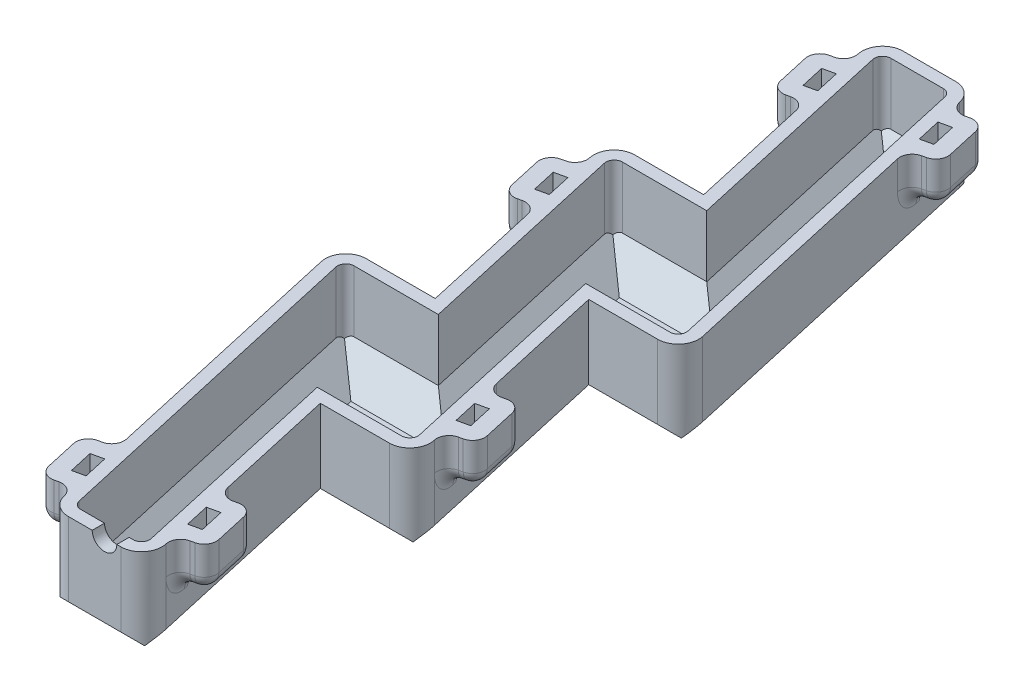
SolidWorks part; units mm, degrees
ref_plane "Front Plane" through (0, 0, 0) normal (0, 0, 1) x (1, 0, 0)
ref_plane "Top Plane" through (0, 0, 0) normal (0, 1, 0) x (1, 0, 0)
ref_plane "Right Plane" through (0, 0, 0) normal (1, 0, 0) x (0, 0, -1)
sketch "Sketch1" plane through (0, 0, 0) normal (0, 1, 0) x (1, 0, 0)
  line L12 (-21.7087, 45.3722) -> (1.3505, 45.3722)
  line L17 (-21.7087, 45.3722) -> (-1.3505, -45.3722)
  line L18 (1.3505, 45.3722) -> (21.7087, -45.3722)
  line L19 (-1.3505, -45.3722) -> (21.7087, -45.3722)
  line L20 (-10.1791, 45.3722) -> (10.1791, -45.3722) construction
  line L21 (32.5125, 9.2556) -> (9.4532, 9.2556)
  line L22 (32.5125, 9.2556) -> (12.1543, 100)
  line L23 (9.4532, 9.2556) -> (-10.905, 100)
  line L24 (12.1543, 100) -> (-10.905, 100)
  line L25 (20.9828, 9.2556) -> (0.6246, 100) construction
  line L26 (-32.5125, -9.2556) -> (-9.4532, -9.2556)
  line L27 (-32.5125, -9.2556) -> (-12.1543, -100)
  line L28 (-9.4532, -9.2556) -> (10.905, -100)
  line L29 (-12.1543, -100) -> (10.905, -100)
  line L30 (-20.9828, -9.2556) -> (-0.6246, -100) construction
  line L31 (1.051, -42.3722) -> (17.9611, -42.3722) construction
  line L32 (1.051, -42.3722) -> (-17.9611, 42.3722) construction
  line L33 (17.9611, -42.3722) -> (-1.051, 42.3722) construction
  line L34 (-17.9611, 42.3722) -> (-1.051, 42.3722) construction
  line L35 (-9.4532, -9.2556) -> (9.4532, 9.2556) construction
  line L36 (9.5061, -42.3722) -> (17.556, -40.5662) construction
  point P7 (0, 0)
  point P20 (-9.5061, 42.3722)
  point P21 (9.5061, -42.3722)
  point P26 (8.4551, 0)
  point P27 (0, 0)
  dimension "D1" = 93
  dimension "D3" = 200
  dimension "D4" = 3
  dimension "D5" = 3
  dimension "D6" = 85
  dimension "14.5" = 16.5
extrude "Boss-Extrude1" add sketch "Sketch1" along normal blind 25 contours L18 | L17 L18 | L17 | L27 region at (0, 0, 0) region at (10.8037, 0, -54.6278) region at (-10.8037, 0, 54.6278)
sketch "Sketch4" plane through (0, 25, 0) normal (0, 1, 0) x (1, 0, 0)
  line L0 (1.051, -42.3722) -> (17.9611, -42.3722)
  line L1 (1.051, -42.3722) -> (-17.9611, 42.3722)
  line L2 (17.9611, -42.3722) -> (-1.051, 42.3722)
  line L3 (-17.9611, 42.3722) -> (-1.051, 42.3722)
  line L4 (11.8547, 12.2556) -> (28.7648, 12.2556)
  line L5 (11.8547, 12.2556) -> (-7.1574, 97)
  line L6 (28.7648, 12.2556) -> (9.7527, 97)
  line L7 (-7.1574, 97) -> (9.7527, 97)
  line L8 (1.2977, 97) -> (20.3098, 12.2556) construction
  line L9 (-28.7648, -12.2556) -> (-11.8547, -12.2556)
  line L10 (-28.7648, -12.2556) -> (-9.7527, -97)
  line L11 (-11.8547, -12.2556) -> (7.1574, -97)
  line L12 (-9.7527, -97) -> (7.1574, -97)
  line L13 (-20.3098, -12.2556) -> (-1.2977, -97) construction
  line L14 (-32.5125, -9.2556) -> (-9.4532, -9.2556) construction
  line L15 (-32.5125, -9.2556) -> (-12.1543, -100) construction
  line L16 (12.1543, 100) -> (-10.905, 100) construction
  line L17 (9.4532, 9.2556) -> (-10.905, 100) construction
  line L18 (-11.8547, -12.2556) -> (-5.7056, -12.2556)
  line L19 (1.051, -42.3722) -> (-5.0982, -42.3722)
  line L20 (11.8547, 12.2556) -> (5.7056, 12.2556)
  line L21 (-1.051, 42.3722) -> (5.0982, 42.3722)
  dimension "D1" = 3
  dimension "D2" = 3
  dimension "D3" = 3
  dimension "D4" = 3
extrude "Cut-Extrude1" cut sketch "Sketch4" against normal blind 22 contours L10 L12 L11 L9 | L19 L1 L18 L11 | L3 L1 L0 L2 | L7 L5 L4 L6 | L21 L2 L20 L5 region at (0, 25, 0) region at (-5.4019, 25, 27.3139) region at (-10.8037, 25, 54.6278) region at (5.4019, 25, -27.3139) region at (10.8037, 25, -54.6278)
chamfer "Chamfer1" distance 7 angle 45 24 edges at (-17.2352, 3, 12.2556) (-11.8333, 3, -15.0583) (-6.4315, 3, -42.3722) (-1.0296, 3, -69.6861) (1.2977, 3, -97) (19.2588, 3, -54.6278) (17.2352, 3, -12.2556) (11.8333, 3, 15.0583) (6.4315, 3, 42.3722) (1.0296, 3, 69.6861) (-1.2977, 3, 97) (-19.2588, 3, 54.6278) (0.6246, 0, -100) (-4.7772, 0, -72.6861) (-10.1791, 0, -45.3722) (-15.581, 0, -18.0583) (-20.9828, 0, 9.2556) (-0.6246, 0, 100) (4.7772, 0, 72.6861) (10.1791, 0, 45.3722) (15.581, 0, 18.0583) (20.9828, 0, -9.2556) (22.3334, 0, -54.6278) (-22.3334, 0, 54.6278)
fillet "Fillet1" radius 2 8 edges at (28.7648, 17.5, -12.2556) (17.9611, 17.5, 42.3722) (7.1574, 17.5, 97) (-9.7527, 17.5, 97) (-28.7648, 17.5, 12.2556) (-17.9611, 17.5, -42.3722) (-7.1574, 17.5, -97) (9.7527, 17.5, -97)
fillet "Fillet2" radius 5 8 edges at (-10.905, 16, -100) (-21.7087, 16, -45.3722) (32.5125, 16, -9.2556) (21.7087, 16, 45.3722) (10.905, 16, 100) (-12.1543, 16, 100) (-32.5125, 16, 9.2556) (12.1543, 16, -100)
sketch "Sketch14" plane through (0, 25, 0) normal (0, 1, 0) x (1, 0, 0)
  line L0 (-15.7112, 89.4459) -> (-8.881, 90.9782)
  line L1 (-15.7112, 89.4459) -> (-12.6466, 75.7855)
  line L2 (-8.881, 90.9782) -> (-8.0054, 87.0753)
  line L3 (-12.6466, 75.7855) -> (-5.8163, 77.3178)
  line L4 (1.3505, 45.3722) -> (-9.5377, 93.9055) construction
  line L5 (13.6872, 93.1673) -> (14.5628, 89.2643)
  line L6 (13.6872, 93.1673) -> (20.5174, 94.6996)
  line L7 (16.7518, 79.5068) -> (23.582, 81.0392)
  line L8 (20.5174, 94.6996) -> (23.582, 81.0392)
  line L9 (31.1452, 15.3501) -> (13.0304, 96.0945) construction
  line L10 (-19.6847, 36.3504) -> (-18.8091, 32.4474)
  line L11 (-19.6847, 36.3504) -> (-26.515, 34.8181)
  line L12 (-16.6201, 22.69) -> (-23.4503, 21.1576)
  line L13 (-26.515, 34.8181) -> (-23.4503, 21.1576)
  line L14 (-20.3414, 39.2777) -> (-9.4532, -9.2556) construction
  line L15 (19.6847, -36.3504) -> (18.8091, -32.4474)
  line L16 (19.6847, -36.3504) -> (26.515, -34.8181)
  line L17 (16.6201, -22.69) -> (23.4503, -21.1576)
  line L18 (26.515, -34.8181) -> (23.4503, -21.1576)
  line L19 (9.4532, 9.2556) -> (20.3414, -39.2777) construction
  line L20 (-13.6872, -93.1673) -> (-14.5628, -89.2643)
  line L21 (-13.6872, -93.1673) -> (-20.5174, -94.6996)
  line L22 (-16.7518, -79.5068) -> (-23.582, -81.0392)
  line L23 (-20.5174, -94.6996) -> (-23.582, -81.0392)
  line L24 (-31.1452, -15.3501) -> (-13.0304, -96.0945) construction
  line L25 (8.881, -90.9782) -> (8.0054, -87.0753)
  line L26 (8.881, -90.9782) -> (15.7112, -89.4459)
  line L27 (5.8163, -77.3178) -> (12.6466, -75.7855)
  line L28 (15.7112, -89.4459) -> (12.6466, -75.7855)
  line L29 (-1.3505, -45.3722) -> (9.5377, -93.9055) construction
  line L30 (-10.9326, 86.4185) -> (-8.0054, 87.0753)
  line L31 (-10.9326, 86.4185) -> (-9.6192, 80.5641)
  line L33 (-9.6192, 80.5641) -> (-6.692, 81.2208)
  line L35 (14.5628, 89.2643) -> (17.49, 89.921)
  line L36 (15.8762, 83.4098) -> (18.8034, 84.0665)
  line L37 (17.49, 89.921) -> (18.8034, 84.0665)
  line L39 (-18.8091, 32.4474) -> (-21.7364, 31.7907)
  line L40 (-17.4957, 26.593) -> (-20.4229, 25.9363)
  line L41 (-21.7364, 31.7907) -> (-20.4229, 25.9363)
  line L43 (17.4957, -26.593) -> (20.4229, -25.9363)
  line L44 (18.8091, -32.4474) -> (21.7364, -31.7907)
  line L45 (20.4229, -25.9363) -> (21.7364, -31.7907)
  line L47 (-15.8762, -83.4098) -> (-18.8034, -84.0665)
  line L48 (-14.5628, -89.2643) -> (-17.49, -89.921)
  line L49 (-18.8034, -84.0665) -> (-17.49, -89.921)
  line L51 (6.692, -81.2208) -> (9.6192, -80.5641)
  line L52 (8.0054, -87.0753) -> (10.9326, -86.4185)
  line L53 (9.6192, -80.5641) -> (10.9326, -86.4185)
  line L54 (-6.692, 81.2208) -> (-5.8163, 77.3178)
  line L55 (15.8762, 83.4098) -> (16.7518, 79.5068)
  line L56 (-17.4957, 26.593) -> (-16.6201, 22.69)
  line L57 (17.4957, -26.593) -> (16.6201, -22.69)
  line L58 (-15.8762, -83.4098) -> (-16.7518, -79.5068)
  line L59 (6.692, -81.2208) -> (5.8163, -77.3178)
  dimension "D1" = 7
  dimension "D2" = 14
  dimension "D3" = 3
  dimension "D4" = 3
  dimension "D5" = 3
  dimension "D6" = 3
  dimension "D7" = 3
  dimension "D8" = 3
  dimension "D9" = 4
  dimension "D10" = 3
  dimension "D11" = 6
  dimension "D12" = 4
  dimension "D13" = 4
  dimension "D14" = 4
  dimension "D15" = 4
  dimension "D16" = 4
extrude "Boss-Extrude2" add sketch "Sketch14" against normal blind 10
fillet "Fillet3" radius 3 54 edges at (5.8163, 20, 77.3178) (8.881, 20, 90.9782) (16.6201, 20, 22.69) (19.6847, 20, 36.3504) (13.6872, 20, -93.1673) (16.7518, 20, -79.5068) (-8.881, 20, -90.9782) (-5.8163, 20, -77.3178) (-19.2469, 15, -34.3989) (-17.0579, 15, -24.6415) (-16.314, 15, 81.4583) (-14.125, 15, 91.2158) (12.6466, 20, 75.7855) (9.2315, 15, 76.5516) (6.2542, 15, 79.2693) (15.7112, 20, 89.4459) (14.1789, 15, 82.6157) (12.2961, 15, 90.2121) (8.4432, 15, 89.0267) (17.0579, 15, 24.6415) (23.4503, 20, 21.1576) (20.0352, 15, 21.9238) (24.9826, 15, 27.9879) (26.515, 20, 34.8181) (23.0998, 15, 35.5843) (19.2469, 15, 34.3989) (23.582, 20, -81.0392) (20.5174, 20, -94.6996) (14.125, 15, -91.2158) (17.1023, 15, -93.9335) (22.0497, 15, -87.8694) (20.1669, 15, -80.273) (16.314, 15, -81.4583) (-8.4432, 15, -89.0267) (-12.2961, 15, -90.2121) (-15.7112, 20, -89.4459) (-14.1789, 15, -82.6157) (-12.6466, 20, -75.7855) (-9.2315, 15, -76.5516) (-6.2542, 15, -79.2693) (-19.6847, 20, -36.3504) (-23.0998, 15, -35.5843) (-26.515, 20, -34.8181) (-24.9826, 15, -27.9879) (-23.4503, 20, -21.1576) (-20.0352, 15, -21.9238) (-16.6201, 20, -22.69) (-16.7518, 20, 79.5068) (-20.1669, 15, 80.273) (-23.582, 20, 81.0392) (-20.5174, 20, 94.6996) (-22.0497, 15, 87.8694) (-17.1023, 15, 93.9335) (-13.6872, 20, 93.1673)
sketch "Sketch16" plane through (0, 0, 100) normal (0, 0, 1) x (1, 0, 0)
  line L0 (-8.1517, 25) -> (4.659, 25) construction
  line L1 (4.659, 7) -> (4.659, 25) construction
  circle A0 centre (0.659, 25) radius 3
  dimension "D1" = 6
  dimension "D2" = 4
extrude "Cut-Extrude2" cut sketch "Sketch16" against normal blind 10
equation "\"D7@Sketch11\"=\"D5@Sketch11\""
equation "\"D8@Sketch11\"=\"D5@Sketch11\""
equation "\"D6@Sketch11\"=\"D5@Sketch11\""
equation "\"D5@Sketch11\"=\"D1@Sketch11\""
equation "\"D4@Sketch11\"=\"D1@Sketch11\""
